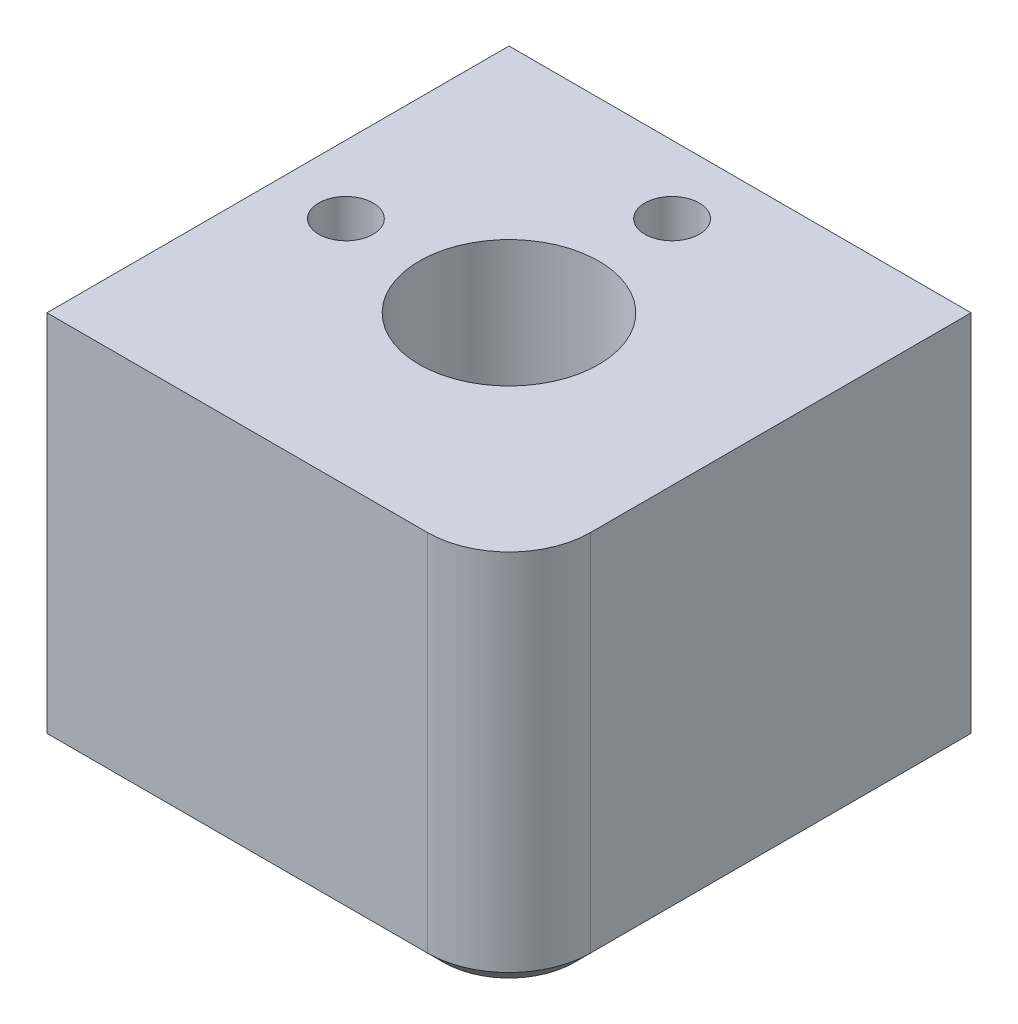
SolidWorks part; units mm, degrees
material "6061-T6 (SS)"
ref_plane "Front Plane" through (0, 0, 0) normal (0, 0, 1) x (1, 0, 0)
ref_plane "Top Plane" through (0, 0, 0) normal (0, 1, 0) x (1, 0, 0)
ref_plane "Right Plane" through (0, 0, 0) normal (1, 0, 0) x (0, 0, -1)
sketch "Base" plane through (0, 0, 0) normal (0, 1, 0) x (1, 0, 0)
  line L1 (-4.25, -4.25) -> (4.25, -4.25)
  line L2 (-4.25, -4.25) -> (-4.25, 4.25)
  line L3 (-4.25, 4.25) -> (4.25, 4.25)
  line L4 (4.25, -4.25) -> (4.25, 4.25)
  line L5 (-4.25, -4.25) -> (4.25, 4.25) construction
  line L6 (-4.25, 4.25) -> (4.25, -4.25) construction
  point P0 (0, 0)
  dimension "D1" = 8.5
  dimension "D2" = 8.5
extrude "Boss-Extrude1" add sketch "Base" against normal blind 8.5
sketch "Cutout" plane through (0, 0, 0) normal (0, 1, 0) x (1, 0, 0)
  line L1 (-4.25, 4.25) -> (2.75, 4.25)
  line L2 (-4.25, 4.25) -> (-4.25, -2.75)
  line L3 (-4.25, -2.75) -> (2.75, -2.75)
  line L4 (2.75, 4.25) -> (2.75, -2.75)
  line L5 (2.75, -2.75) -> (-4.25, 4.25) construction
  line L6 (2.75, 4.25) -> (-4.25, -2.75) construction
  point P5 (-0.75, 0.75)
  dimension "D1" = 7
  dimension "D2" = 7
extrude "Cut-Extrude1" cut sketch "Cutout" against normal blind 1.5
sketch "Sketch3" plane through (2.75, 0, 0) normal (-1, 0, 0) x (0, 0, 1)
  line L0 (2.75, -1.5) -> (-4.25, -1.5) construction
  line L1 (-4.25, 0) -> (-2.75, 0)
  line L2 (-4.25, 0) -> (-4.25, -1.5)
  line L3 (-4.25, -1.5) -> (-2.75, -1.5)
  line L4 (-2.75, 0) -> (-2.75, -1.5)
  dimension "D1" = 1.5
extrude "Cut-Extrude2" cut sketch "Sketch3" against normal through all
ref_axis "Axis2" through (2.75, -1.5, 2.75) along (-0.7071, 0, -0.7071)
ref_plane "Plane1" through (0, 0, 0) normal (0.7071, 0, -0.7071) x (-0.7071, 0, -0.7071)
mirror "Mirror1" about plane through (0, 0, 0) normal (0.7071, 0, -0.7071) of "Cut-Extrude2"
fillet "Fillet3" radius 0.508 1 edges at (2.75, -0.75, 2.75)
fillet "Fillet4" radius 1.5 1 edges at (4.25, -4.25, 4.25)
hole_wizard "M4 Tapped Hole1" positions "Sketch12" profile "Sketch13" tap size "M4" standard "AS"
sketch "Sketch12" plane through (0, -1.5, 0) normal (0, 1, 0) x (1, 0, 0)
  line L3 (4.25, -2.75) -> (4.25, 2.75) construction
  line L4 (-2.75, -4.25) -> (2.75, -4.25) construction
  point P0 (0, 0)
  dimension "D1" = 4.25
  dimension "D2" = 4.25
cosmetic thread "Hole Thread1" parameters "D1"=5, "D2"=4
sketch "Sketch13" plane through (0, -1.5, 0) normal (1, 0, 0) x (0, 0, 1)
  line L0 (0, 0) -> (0, 5.9914)
  line L1 (0, 5.9914) -> (1.65, 5)
  line L2 (1.65, 5) -> (1.65, 0)
  line L5 (1.65, 0) -> (0, 0)
  line L10 (0, 5.9914) -> (-1.65, 5) construction
  line L11 (0, -6.35) -> (0, 107.95) construction
  dimension "Tap Drill Dia." = 3.3
  dimension "Tap Drill Depth" = 5
  dimension "Drill Angle" = 118
sketch "Sketch14" plane through (0, 0, 0) normal (0, 1, 0) x (1, 0, 0)
  line L6 (-2.75, -4.25) -> (2.75, -4.25)
  line L7 (4.25, -2.75) -> (4.25, 2.75)
  line L8 (4.25, 2.75) -> (2.75, 2.75)
  line L9 (2.75, 2.75) -> (2.75, -2.242)
  line L10 (2.242, -2.75) -> (-2.75, -2.75)
  line L11 (-2.75, -2.75) -> (-2.75, -4.25)
  line L12 (-2.75, -4.25) -> (2.75, -4.25)
  line L13 (4.25, -2.75) -> (4.25, 2.75)
  line L14 (4.25, 2.75) -> (2.75, 2.75)
  line L15 (2.75, 2.75) -> (2.75, -2.242)
  line L16 (2.242, -2.75) -> (-2.75, -2.75)
  line L17 (-2.75, -2.75) -> (-2.75, -4.25)
  arc A2 (2.75, -4.25) -> (4.25, -2.75) centre (2.75, -2.75) ccw
  arc A3 (2.242, -2.75) -> (2.75, -2.242) centre (2.242, -2.242) ccw
  arc A4 (2.75, -4.25) -> (4.25, -2.75) centre (2.75, -2.75) ccw
  arc A5 (2.242, -2.75) -> (2.75, -2.242) centre (2.242, -2.242) ccw
  dimension "D1" = 0
extrude "Cut-Extrude3" cut sketch "Sketch14" against normal up to surface (1.5 mm away) up to face at (0, -1.5, 1.65)
chamfer "Chamfer1" distance 0.3 angle 45 5 edges at (-4.25, -8.5, 0) (-0.75, -8.5, 4.25) (3.8107, -8.5, 3.8107) (4.25, -8.5, -0.75) (0, -8.5, -4.25)
sketch "Sketch16" plane through (0, -1.5, 0) normal (0, 1, 0) x (1, 0, 0)
  line L0 (0, 4.25) -> (0, 0) construction
  line L2 (4.25, 4.25) -> (-4.25, 4.25) construction
  line L3 (0, 0) -> (-4.25, 0) construction
  line L4 (-4.25, 4.25) -> (-4.25, -4.25) construction
  circle A0 centre (0, 3) radius 0.5
  circle A1 centre (-3, 0) radius 0.5
  point P10 (0, 0)
  point P15 (0, 0)
  dimension "D1" = 1
  dimension "D2" = 1.25
  dimension "D3" = 1.25
extrude "Cut-Extrude4" cut sketch "Sketch16" against normal blind 2.54
